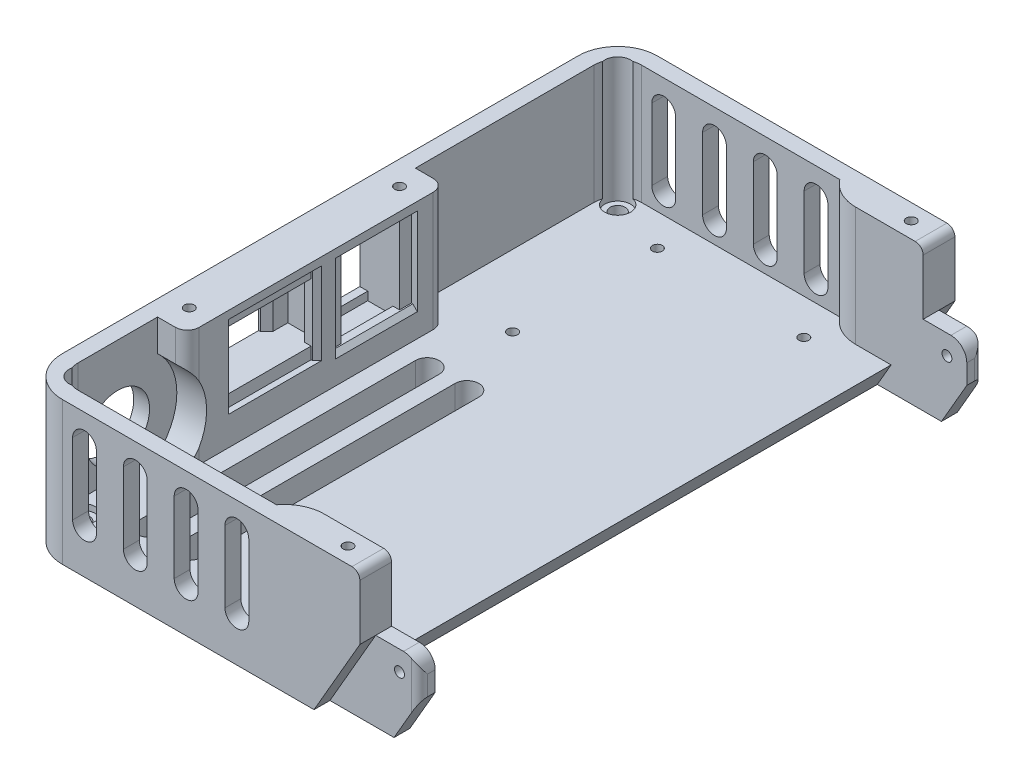
SolidWorks part; units mm, degrees
ref_plane "Front" through (0, 0, 0) normal (0, 0, 1) x (1, 0, 0)
ref_plane "Top" through (0, 0, 0) normal (0, 1, 0) x (1, 0, 0)
ref_plane "Right" through (0, 0, 0) normal (1, 0, 0) x (0, 0, -1)
sketch "Sketch1" plane through (0, 0, 0) normal (0, 0, 1) x (1, 0, 0)
  line L0 (0, 0) -> (73.453, 0)
  line L1 (73.453, 0) -> (85, 20)
  line L2 (85, 20) -> (0, 20)
  line L3 (0, 20) -> (0, 0)
  dimension "D1" = 85
  dimension "D2" = 20
  dimension "D3" = 60
extrude "Boss-Extrude1" add sketch "Sketch1" along normal blind 150
fillet "Fillet1" radius 10 2 edges at (0, 10, 0) (0, 10, 150)
sketch "Sketch2" plane through (0, 20, 0) normal (0, 1, 0) x (1, 0, 0)
  line L0 (85, -4) -> (10, -4)
  line L1 (4, -10) -> (4, -140)
  line L2 (10, -146) -> (85, -146)
  line L3 (85, -146) -> (85, -4)
  line L12 (85, -150) -> (85, 0) construction
  line L13 (0, -140) -> (0, -10) construction
  line L14 (85, 0) -> (10, 0) construction
  line L15 (85, -150) -> (10, -150) construction
  arc A0 (10, -4) -> (4, -10) centre (10, -10) ccw
  arc A1 (4, -140) -> (10, -146) centre (10, -140) ccw
  dimension "D4" = 6
  dimension "D5" = 6
  dimension "D6" = 6
  dimension "D8" = 6
  dimension "D9" = 6
  dimension "D1" = 4
  dimension "D2" = 4
  dimension "D3" = 4
  dimension "D7" = 6
extrude "Cut-Extrude1" cut sketch "Sketch2" against normal offset from surface (14 mm away) 6 up to face at (27.1273, 0, 75)
sketch "Sketch3" plane through (0, 0, 0) normal (0, -1, 0) x (1, 0, 0)
  line L0 (76.9171, 146) -> (85, 146) construction
  line L1 (60, 146) -> (96, 146)
  line L2 (60, 146) -> (60, 142)
  line L3 (60, 142) -> (96, 142)
  line L4 (96, 146) -> (96, 142)
  line L5 (85, 150) -> (85, 146) construction
  line L6 (0, 75) -> (117.2937, 75) construction
  line L7 (0, 140) -> (0, 10) construction
  line L8 (96, 4) -> (96, 8)
  line L9 (60, 8) -> (96, 8)
  line L10 (60, 4) -> (60, 8)
  line L11 (60, 4) -> (96, 4)
  dimension "D1" = 4
  dimension "D2" = 11
  dimension "D3" = 25
extrude "Boss-Extrude2" add sketch "Sketch3" against normal up to surface (20 mm away) up to face at (31.781, 20, 75)
fillet "Fillet2" radius 10 2 edges at (60, 13, 142) (60, 13, 8)
sketch "Sketch4" plane through (0, 0, 4) normal (0, 0, -1) x (-1, 0, 0)
  line L0 (-89.6188, 0) -> (-96, 11.0526)
  line L1 (-73.453, 0) -> (-96, 0) construction
  line L2 (-96, 20) -> (-96, 0) construction
  line L3 (-85, 20) -> (-73.453, 0) construction
  line L4 (-96, 11.0526) -> (-96, 0)
  line L5 (-96, 0) -> (-89.6188, 0)
  dimension "D1" = 14
extrude "Cut-Extrude2" cut sketch "Sketch4" against normal through all
fillet "Fillet3" radius 4 2 edges at (96, 20, 144) (96, 20, 6)
sketch "Sketch5" plane through (0, 0, 4) normal (0, 0, -1) x (-1, 0, 0)
  line L0 (-92, 20) -> (-85, 20) construction
  line L1 (-96, 16) -> (-96, 11.0526) construction
  circle A0 centre (-91, 15) radius 1.25
  point P6 (-96, 13.5263)
  dimension "D1" = 2.5
  dimension "D2" = 5
  dimension "D3" = 5
extrude "Cut-Extrude3" cut sketch "Sketch5" against normal through all
fillet "Fillet4" radius 2 2 edges at (96, 13.5263, 146) (96, 13.5263, 4) tangent propagation no
sketch "Sketch6" plane through (0, 6, 0) normal (0, 1, 0) x (1, 0, 0)
  line L0 (0, -140) -> (0, -10) construction
  line L1 (0, -120) -> (11.5, -120)
  line L2 (0, -120) -> (0, -55)
  line L3 (0, -55) -> (11.5, -55)
  line L4 (11.5, -120) -> (11.5, -55)
  line L5 (85, -150) -> (10, -150) construction
  dimension "D1" = 11.5
  dimension "D2" = 65
  dimension "D3" = 30
extrude "Boss-Extrude3" add sketch "Sketch6" along normal blind 30
ref_plane "Plane4" through (0, 0, 65) normal (0, 0, 1) x (1, 0, 0)
sketch "Sketch12" plane through (0, 0, 65) normal (0, 0, 1) x (0, -1, 0)
  line L0 (-33.95, 11.55) -> (-11.85, 11.55)
  line L1 (-29.65, 0) -> (-13.15, 0)
  line L2 (-29.65, 0.4) -> (-31.25, 2)
  line L3 (-31.25, 2) -> (-35, 2)
  line L4 (-35, 2) -> (-35, 8.35)
  line L5 (-35, 8.35) -> (-32.75, 8.35)
  line L6 (-32.75, 8.35) -> (-32.75, 10.35)
  line L7 (-32.75, 10.35) -> (-33.95, 11.55)
  line L8 (-29.65, 0) -> (-29.65, 0.4)
  line L9 (-11.85, 11.55) -> (-13.05, 10.35)
  line L10 (-13.05, 10.35) -> (-13.05, 8.35)
  line L11 (-13.05, 8.35) -> (-11.05, 8.35)
  line L12 (-11.05, 8.35) -> (-11.05, 2)
  line L13 (-11.05, 2) -> (-13.15, 2)
  line L14 (-13.15, 2) -> (-13.15, 0)
  line L15 (-36, 0) -> (-20, 0) construction
  line L16 (-36, 0) -> (-36, 11.5) construction
  dimension "D1" = 11.55
  dimension "D2" = 2
  dimension "D3" = 45
  dimension "D4" = 6.35
  dimension "D5" = 2
  dimension "D6" = 0.4
  dimension "D7" = 45
  dimension "D8" = 3.2
  dimension "D9" = 2
  dimension "D10" = 45
  dimension "D11" = 6.35
  dimension "D12" = 2
  dimension "D13" = 16.5
  dimension "D14" = 2.1
  dimension "D15" = 5.35
  dimension "D16" = 2
  dimension "D17" = 1.2
  dimension "D18" = 2.25
  dimension "D19" = 1.05
  dimension "D20" = 1
extrude "Cut-Extrude7" cut sketch "Sketch12" along normal blind 14.7
sketch "Sketch13" plane through (0, 0, 65) normal (0, 0, 1) x (1, 0, 0)
  line L0 (10.35, 13.05) -> (11.5, 11.9) construction
  line L1 (11.5, 11.9) -> (11.5, 33.9) construction
  line L2 (11.5, 33.9) -> (10.35, 32.75) construction
  line L3 (10.35, 13.05) -> (11.5, 11.9)
  line L4 (11.5, 11.9) -> (11.5, 33.9)
  line L5 (11.5, 33.9) -> (10.35, 32.75)
  line L6 (10.35, 32.75) -> (10, 32.75)
  line L7 (10.35, 32.75) -> (8.35, 32.75) construction
  line L8 (10, 32.75) -> (10, 13.05)
  line L9 (8.35, 13.05) -> (10.35, 13.05) construction
  line L10 (10, 13.05) -> (10.35, 13.05)
  dimension "D1" = 1.5
extrude "Cut-Extrude8" cut sketch "Sketch13" against normal blind 3 and the other way blind 17.7
ref_plane "Plane5" through (0, 31, 0) normal (0, 1, 0) x (1, 0, 0)
sketch "Sketch14" plane through (175.4771, 31, 46.4652) normal (0, 1, 0) x (0, 0, 1)
  line L0 (39.6348, -163.9271) -> (61.8348, -163.9271)
  line L1 (44.0348, -175.4771) -> (60.5348, -175.4771)
  line L2 (44.0348, -175.0771) -> (42.4348, -173.4771)
  line L3 (42.4348, -173.4771) -> (38.6848, -173.4771)
  line L4 (38.6848, -173.4771) -> (38.6848, -167.1271)
  line L5 (38.6848, -167.1271) -> (40.8348, -167.1271)
  line L6 (40.8348, -167.1271) -> (40.8348, -165.1271)
  line L7 (40.8348, -165.1271) -> (39.6348, -163.9271)
  line L8 (44.0348, -175.4771) -> (44.0348, -175.0771)
  line L9 (61.8348, -163.9271) -> (60.6348, -165.1271)
  line L10 (60.6348, -165.1271) -> (60.6348, -167.1271)
  line L11 (60.6348, -167.1271) -> (62.5348, -167.1271)
  line L12 (62.5348, -167.1271) -> (62.5348, -173.4771)
  line L13 (62.5348, -173.4771) -> (60.5348, -173.4771)
  line L14 (60.5348, -173.4771) -> (60.5348, -175.4771)
  line L15 (73.5348, -175.4771) -> (8.5348, -175.4771) construction
  line L16 (73.5348, -175.4771) -> (73.5348, -163.9771) construction
  dimension "D1" = 11.55
  dimension "D2" = 2
  dimension "D3" = 45
  dimension "D4" = 6.35
  dimension "D5" = 2
  dimension "D6" = 0.4
  dimension "D7" = 45
  dimension "D8" = 3.2
  dimension "D9" = 2
  dimension "D10" = 45
  dimension "D11" = 6.35
  dimension "D12" = 2
  dimension "D13" = 16.5
  dimension "D14" = 2
  dimension "D15" = 5.35
  dimension "D16" = 1.9
  dimension "D17" = 1.2
  dimension "D18" = 2.15
  dimension "D19" = 0.95
  dimension "D20" = 11
extrude "Cut-Extrude9" cut sketch "Sketch14" against normal blind 14.7
sketch "Sketch15" plane through (0, 16.3, 0) normal (0, 1, 0) x (1, 0, 0)
  line L0 (10, -87.3) -> (10, -107.1)
  line L15 (11.5, -108.25) -> (11.5, -86.15)
  line L16 (11.5, -86.15) -> (10.35, -87.3)
  line L17 (10.35, -87.3) -> (8.35, -87.3)
  line L18 (8.35, -87.3) -> (8.35, -85.15)
  line L19 (8.35, -85.15) -> (2, -85.15)
  line L20 (2, -85.15) -> (2, -88.9)
  line L21 (2, -88.9) -> (0.4, -90.5)
  line L22 (0.4, -90.5) -> (0, -90.5)
  line L23 (0, -90.5) -> (0, -107)
  line L24 (0, -107) -> (2, -107)
  line L25 (2, -107) -> (2, -109)
  line L26 (2, -109) -> (8.35, -109)
  line L27 (8.35, -109) -> (8.35, -107.1)
  line L28 (8.35, -107.1) -> (10.35, -107.1)
  line L29 (10.35, -107.1) -> (11.5, -108.25)
  line L30 (11.5, -108.25) -> (11.5, -86.15)
  line L31 (11.5, -86.15) -> (10.35, -87.3)
  line L32 (10.35, -87.3) -> (10, -87.3)
  line L43 (10, -107.1) -> (10.35, -107.1)
  line L44 (10.35, -107.1) -> (11.5, -108.25)
  dimension "D2" = 1.5
  dimension "D1" = 0
extrude "Cut-Extrude10" cut sketch "Sketch15" against normal blind 3 and the other way blind 17.7
sketch "Sketch16" plane through (0, 6, 0) normal (0, 1, 0) x (1, 0, 0)
  line L0 (85, 0) -> (10, 0) construction
  line L1 (85, -150) -> (10, -150) construction
  line L2 (76.9171, -142) -> (76.9171, -8) construction
  line L3 (0, -55) -> (0, -10) construction
  circle A0 centre (22, -12) radius 1.25
  circle A1 centre (22, -48.5) radius 1.25
  circle A2 centre (59.9171, -13) radius 1.25
  circle A3 centre (59.9171, -137) radius 1.25
  point P0 (22, -12)
  point P1 (22, -48.5)
  point P3 (59.9171, -13)
  point P5 (59.9171, -137)
  dimension "D8" = 2.5
  dimension "D9" = 2.5
  dimension "D10" = 2.5
  dimension "D11" = 2.5
  dimension "D1" = 124
  dimension "D2" = 13
  dimension "D3" = 13
  dimension "D4" = 17
  dimension "D5" = 36.5
  dimension "D6" = 22
  dimension "D7" = 12
sketch "Sketch25" plane through (0, 0, 109) normal (0, 0, -1) x (-1, 0, 0)
  line L4 (-2, 31) -> (-8.35, 31)
  line L5 (-8.35, 31) -> (-8.35, 16.3)
  line L6 (-8.35, 16.3) -> (-2, 16.3)
  line L7 (-2, 16.3) -> (-2, 31)
  line L8 (-2, 31) -> (-8.35, 31)
  line L9 (-8.35, 31) -> (-8.35, 16.3)
  line L10 (-8.35, 16.3) -> (-2, 16.3)
  line L11 (-2, 16.3) -> (-2, 31)
  dimension "D1" = 0
extrude "Cut-Extrude19" cut sketch "Sketch25" against normal blind 1.5
sketch "Sketch27" plane through (0, 0, 107.1) normal (0, 0, -1) x (-1, 0, 0)
  line L0 (-10.35, 34) -> (-12.5261, 34)
  line L1 (-12.5261, 34) -> (-12.5261, 13.3)
  line L2 (-12.5261, 13.3) -> (-10.35, 13.3)
  line L8 (-10.35, 34) -> (-10.35, 13.3)
  line L9 (-10.35, 13.3) -> (-10, 13.3)
  line L10 (-10, 13.3) -> (-10, 16.3)
  line L11 (-10, 16.3) -> (-8.35, 16.3)
  line L12 (-8.35, 16.3) -> (-8.35, 31)
  line L13 (-8.35, 31) -> (-10, 31)
  line L14 (-10, 31) -> (-10, 34)
  line L15 (-10, 34) -> (-10.35, 34)
  line L17 (-10.35, 13.3) -> (-10, 13.3)
  line L18 (-10, 13.3) -> (-10, 16.3)
  line L19 (-10, 16.3) -> (-8.35, 16.3)
  line L20 (-8.35, 16.3) -> (-8.35, 31)
  line L21 (-8.35, 31) -> (-10, 31)
  line L22 (-10, 31) -> (-10, 34)
  line L23 (-10, 34) -> (-10.35, 34)
  dimension "D1" = 0
extrude "Cut-Extrude20" cut sketch "Sketch27" against normal blind 1.5
chamfer "Chamfer1" distance 1 angle 45 1 edges at (11.5, 23.65, 108.6)
extrude "Cut-Extrude11" cut sketch "Sketch16" against normal through all
sketch "Sketch17" plane through (0, 20, 0) normal (0, 1, 0) x (1, 0, 0)
  line L0 (92, -142) -> (68, -142) construction
  line L9 (0, -55) -> (4, -55)
  line L10 (4, -55) -> (4, -10)
  line L11 (10, -4) -> (60, -4)
  line L12 (68, -8) -> (92, -8)
  line L13 (92, -8) -> (92, -4)
  line L14 (92, -4) -> (85, -4)
  line L15 (85, -4) -> (85, 0)
  line L16 (85, 0) -> (10, 0)
  line L17 (0, -10) -> (0, -55)
  line L18 (0, -55) -> (4, -55)
  line L19 (4, -55) -> (4, -10)
  line L20 (10, -4) -> (60, -4)
  line L21 (68, -8) -> (85, -8)
  line L24 (85, -8) -> (85, 0)
  line L25 (85, 0) -> (10, 0)
  line L26 (0, -10) -> (0, -55)
  line L27 (4, -120) -> (0, -120)
  line L28 (0, -120) -> (0, -140)
  line L29 (10, -150) -> (85, -150)
  line L30 (85, -150) -> (85, -146)
  line L31 (85, -146) -> (92, -146)
  line L32 (92, -146) -> (92, -142)
  line L33 (92, -142) -> (68, -142)
  line L34 (60, -146) -> (10, -146)
  line L35 (4, -140) -> (4, -120)
  line L36 (4, -120) -> (0, -120)
  line L37 (0, -120) -> (0, -140)
  line L38 (10, -150) -> (85, -150)
  line L39 (85, -150) -> (85, -142)
  line L42 (85, -142) -> (68, -142)
  line L43 (60, -146) -> (10, -146)
  line L44 (4, -140) -> (4, -120)
  arc A3 (10, -4) -> (4, -10) centre (10, -10) ccw
  arc A4 (60, -4) -> (68, -8) centre (68, 2) ccw
  arc A5 (10, 0) -> (0, -10) centre (10, -10) ccw
  arc A6 (10, -4) -> (4, -10) centre (10, -10) ccw
  arc A7 (60, -4) -> (68, -8) centre (68, 2) ccw
  arc A8 (10, 0) -> (0, -10) centre (10, -10) ccw
  arc A9 (0, -140) -> (10, -150) centre (10, -140) ccw
  arc A10 (68, -142) -> (60, -146) centre (68, -152) ccw
  arc A11 (4, -140) -> (10, -146) centre (10, -140) ccw
  arc A12 (0, -140) -> (10, -150) centre (10, -140) ccw
  arc A13 (68, -142) -> (60, -146) centre (68, -152) ccw
  arc A14 (4, -140) -> (10, -146) centre (10, -140) ccw
  dimension "D1" = 0
  dimension "D2" = 0
extrude "Boss-Extrude4" add sketch "Sketch17" along normal up to surface (16 mm away) up to face at (5.75, 36, 87.5)
fillet "Fillet5" radius 3 2 edges at (11.5, 21, 120) (11.5, 21, 55)
sketch "Sketch18" plane through (0, 6, 0) normal (0, 1, 0) x (1, 0, 0)
  line L0 (19, -67) -> (19, -137) construction
  line L1 (22, -67) -> (22, -137)
  line L2 (16, -67) -> (16, -137)
  line L3 (85, -150) -> (10, -150) construction
  line L4 (0, -10) -> (0, -140) construction
  line L5 (29, -67) -> (29, -137) construction
  line L6 (32, -67) -> (32, -137)
  line L7 (26, -67) -> (26, -137)
  arc A0 (22, -67) -> (16, -67) centre (19, -67) ccw
  arc A1 (16, -137) -> (22, -137) centre (19, -137) ccw
  arc A2 (32, -67) -> (26, -67) centre (29, -67) ccw
  arc A3 (26, -137) -> (32, -137) centre (29, -137) ccw
  point P2 (19, -102)
  point P15 (29, -102)
  dimension "D3" = 13
  dimension "D1" = 6
  dimension "D2" = 70
  dimension "D4" = 19
  dimension "D5" = 2
extrude "Cut-Extrude12" cut sketch "Sketch18" against normal through all
sketch "Sketch19" plane through (0, 0, 0) normal (0, -1, 0) x (1, 0, 0)
  line L0 (0, 140) -> (0, 10) construction
  line L1 (10, 150) -> (73.453, 150) construction
  line L2 (10, 0) -> (73.453, 0) construction
  circle A0 centre (7.5, 142.5) radius 1.9
  circle A1 centre (7.5, 7.5) radius 1.9
  point P0 (7.5, 7.5)
  point P1 (7.5, 142.5)
  dimension "D4" = 3.8
  dimension "D5" = 3.8
  dimension "D1" = 7.5
  dimension "D2" = 7.5
  dimension "D3" = 7.5
extrude "Cut-Extrude13" cut sketch "Sketch19" against normal through all
sketch "Sketch20" plane through (0, 36, 0) normal (0, 1, 0) x (1, 0, 0)
  circle A0 centre (7.5, -7.5) radius 3.25
  circle A1 centre (7.5, -142.5) radius 3.25
  dimension "D1" = 6.5
  dimension "D2" = 6.5
extrude "Cut-Extrude14" cut sketch "Sketch20" against normal offset from surface (31.5 mm away) 1.5 up to face at (7.5, 6, 144.4) offset beyond the face yes
sketch "Sketch21" plane through (0, 0, 146) normal (0, 0, -1) x (-1, 0, 0)
  line L0 (-54, 29) -> (-54, 11) construction
  line L1 (-51, 29) -> (-51, 11)
  line L2 (-57, 29) -> (-57, 11)
  line L3 (-10, 36) -> (-60, 36) construction
  line L4 (-60, 36) -> (-60, 6) construction
  line L5 (-41.2, 29) -> (-41.2, 11) construction
  line L6 (-38.2, 29) -> (-38.2, 11)
  line L7 (-44.2, 29) -> (-44.2, 11)
  line L8 (-28.4, 29) -> (-28.4, 11) construction
  line L9 (-25.4, 29) -> (-25.4, 11)
  line L10 (-31.4, 29) -> (-31.4, 11)
  line L11 (-15.6, 29) -> (-15.6, 11) construction
  line L12 (-12.6, 29) -> (-12.6, 11)
  line L13 (-18.6, 29) -> (-18.6, 11)
  arc A0 (-51, 29) -> (-57, 29) centre (-54, 29) ccw
  arc A1 (-57, 11) -> (-51, 11) centre (-54, 11) ccw
  arc A2 (-38.2, 29) -> (-44.2, 29) centre (-41.2, 29) ccw
  arc A3 (-44.2, 11) -> (-38.2, 11) centre (-41.2, 11) ccw
  arc A4 (-25.4, 29) -> (-31.4, 29) centre (-28.4, 29) ccw
  arc A5 (-31.4, 11) -> (-25.4, 11) centre (-28.4, 11) ccw
  arc A6 (-12.6, 29) -> (-18.6, 29) centre (-15.6, 29) ccw
  arc A7 (-18.6, 11) -> (-12.6, 11) centre (-15.6, 11) ccw
  point P2 (-54, 20)
  point P15 (-41.2, 20)
  point P22 (-28.4, 20)
  point P29 (-15.6, 20)
  dimension "D1" = 18
  dimension "D2" = 6
  dimension "D3" = 7
  dimension "D4" = 6
  dimension "D5" = 4
extrude "Cut-Extrude15" cut sketch "Sketch21" against normal through all and the other way through all
sketch "Sketch22" plane through (0, 36, 0) normal (0, 1, 0) x (1, 0, 0)
  line L0 (0, -10) -> (0, -140) construction
  line L1 (4, -120) -> (8.5, -120) construction
  line L2 (8.5, -55) -> (4, -55) construction
  line L3 (85, -150) -> (10, -150) construction
  line L4 (10, 0) -> (85, 0) construction
  line L5 (85, 0) -> (85, -8) construction
  line L6 (85, -142) -> (85, -150) construction
  circle A0 centre (78, -4) radius 1.25
  circle A1 centre (78, -146) radius 1.25
  circle A2 centre (6, -114) radius 1.25
  circle A3 centre (6, -61) radius 1.25
  point P20 (85, -4)
  dimension "D1" = 2.5
  dimension "D2" = 2.5
  dimension "D3" = 2.5
  dimension "D4" = 2.5
  dimension "D5" = 6
  dimension "D6" = 6
  dimension "D7" = 6
  dimension "D8" = 6
  dimension "D9" = 4
  dimension "D10" = 4
  dimension "D11" = 7
  dimension "D12" = 7
extrude "Cut-Extrude16" cut sketch "Sketch22" against normal blind 8
fillet "Fillet6" radius 2 2 edges at (85, 36, 4) (85, 36, 146)
sketch "Sketch23" plane through (4, 0, 0) normal (1, 0, 0) x (0, 0, -1)
  line L0 (-140, 6) -> (-120, 6) construction
  line L4 (-140, 6) -> (-140, 36) construction
  circle A0 centre (-130, 17) radius 8
  dimension "D1" = 16
  dimension "D3" = 10
  dimension "D2" = 11
extrude "Cut-Extrude17" cut sketch "Sketch23" against normal through all
sketch "Sketch24" plane through (11.5, 0, 0) normal (1, 0, 0) x (0, 0, -1)
  line L0 (-120, 6) -> (-120, 28)
  line L1 (-120, 36) -> (-120, 6) construction
  line L2 (-140, 6) -> (-140, 28)
  line L3 (-140, 6) -> (-140, 36) construction
  arc A0 (-140, 28) -> (-140, 6) centre (-130, 17) ccw
  arc A1 (-120, 6) -> (-120, 28) centre (-130, 17) ccw
extrude "Cut-Extrude18" cut sketch "Sketch24" against normal up to surface (7.5 mm away) up to face at (4, 25, 130)
